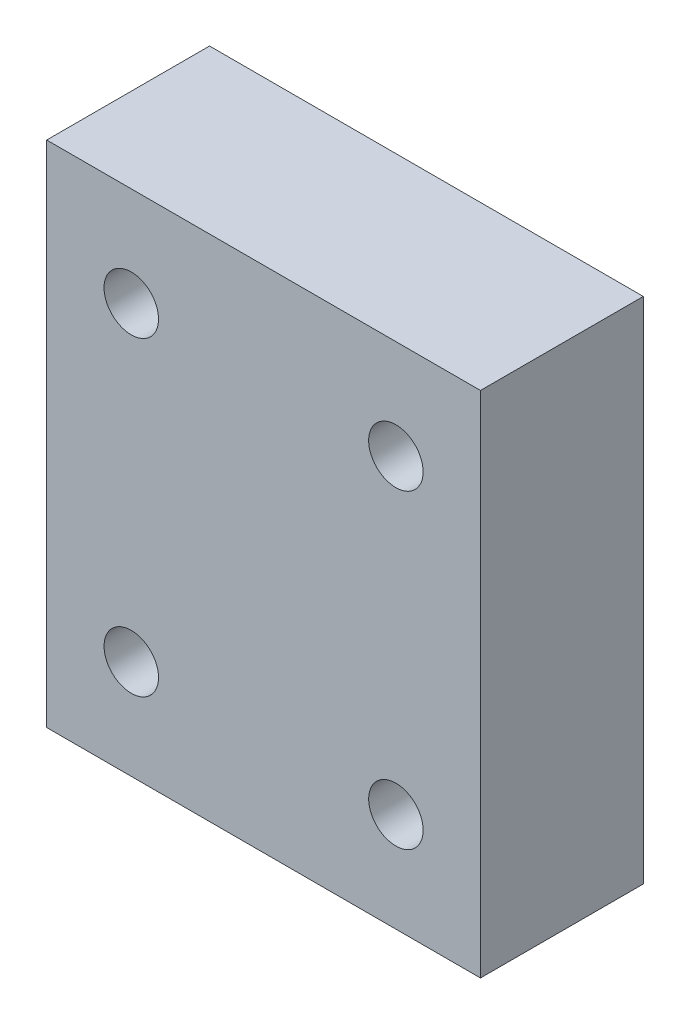
SolidWorks part; units mm, degrees
ref_plane "Front Plane" through (0, 0, 0) normal (0, 0, 1) x (1, 0, 0)
ref_plane "Top Plane" through (0, 0, 0) normal (0, 1, 0) x (1, 0, 0)
ref_plane "Right Plane" through (0, 0, 0) normal (1, 0, 0) x (0, 0, -1)
sketch "Sketch1" plane through (0, 0, 0) normal (0, 0, 1) x (1, 0, 0)
  line L0 (0, 25) -> (0, -25) construction
  line L1 (21.3115, 25) -> (-21.3115, 25)
  line L2 (21.3115, 25) -> (21.3115, -25)
  line L3 (21.3115, -25) -> (-21.3115, -25)
  line L4 (-21.3115, 25) -> (-21.3115, -25)
  line L5 (21.3115, 25) -> (-21.3115, -25) construction
  line L6 (21.3115, -25) -> (-21.3115, 25) construction
  line L7 (-21.3115, 0) -> (21.3115, 0) construction
  circle A0 centre (-13, -15.25) radius 2.677
  circle A1 centre (13, -15.25) radius 2.677
  circle A2 centre (13, 15.25) radius 2.677
  circle A3 centre (-13, 15.25) radius 2.677
  point P0 (0, 0)
  dimension "D1" = 30.5
  dimension "D2" = 26
  dimension "D3" = 50
extrude "Boss-Extrude1" add sketch "Sketch1" along normal blind 16
sketch "Sketch2" plane through (0, 0, 0) normal (0, 0, 1) x (1, 0, 0)
  circle A0 centre (0, 0) radius 11
  dimension "D1" = 22
extrude "Cut-Extrude2" cut sketch "Sketch2" along normal blind 11
sketch "Sketch3" plane through (0, 0, 0) normal (0, 0, -1) x (-1, 0, 0)
  line L0 (0, 0) -> (-18.0234, 0) construction
  line L1 (0, 0) -> (0, 5.0894) construction
  circle A0 centre (-15, 0) radius 1.75
  circle A1 centre (15, 0) radius 1.75
  dimension "D1" = 15
  dimension "D2" = 3.5
extrude "Cut-Extrude3" cut sketch "Sketch3" against normal blind 10
